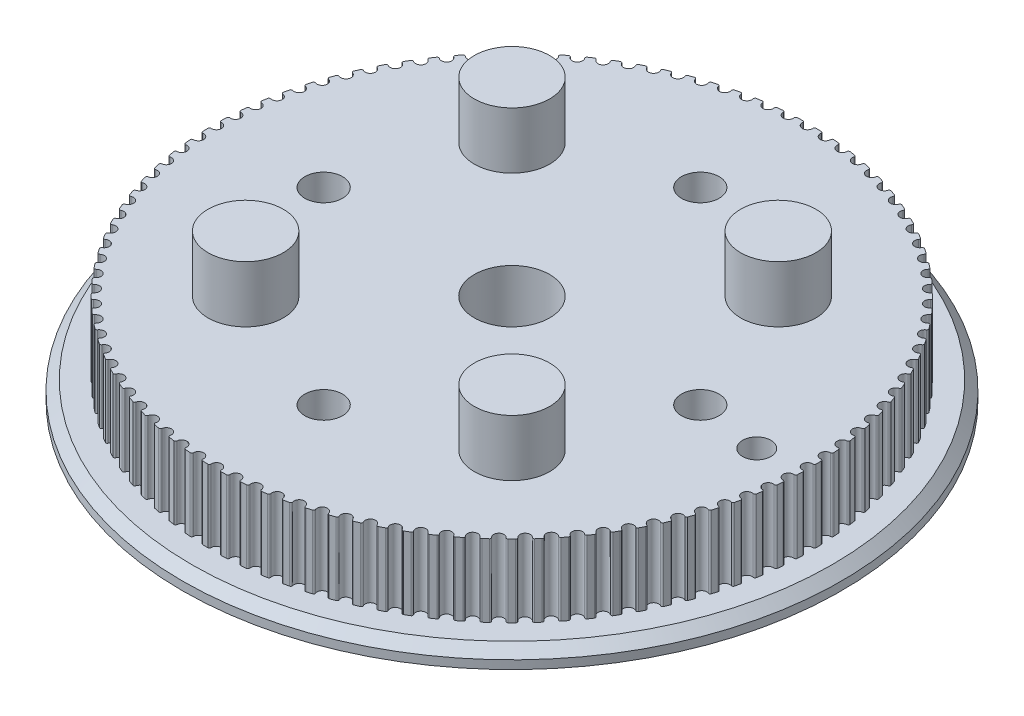
SolidWorks part; units mm, degrees
material "PLA Generic"
ref_plane "Front Plane" through (0, 0, 0) normal (0, 0, 1) x (1, 0, 0)
ref_plane "Top Plane" through (0, 0, 0) normal (0, 1, 0) x (1, 0, 0)
ref_plane "Right Plane" through (0, 0, 0) normal (1, 0, 0) x (0, 0, -1)
sketch "Sketch1" plane through (0, 0, 0) normal (0, 1, 0) x (1, 0, 0)
  circle A0 centre (0, 0) radius 31.6
  circle A1 centre (0, 0) radius 4
  dimension "D1" = 63.2
  dimension "D2" = 8
extrude "Boss-Extrude1" add sketch "Sketch1" along normal blind 7.7
sketch "Sketch2" plane through (0, 0, 0) normal (0, -1, 0) x (1, 0, 0)
  circle A0 centre (0, 0) radius 31.39 construction
  circle A1 centre (0, 31.39) radius 0.55
  circle A2 centre (0, 0) radius 31.39 construction
  circle A4 centre (0, 0) radius 31.39 construction
  circle A6 centre (0, 0) radius 31.39 construction
  circle A8 centre (0, 0) radius 31.39 construction
  circle A10 centre (0, 0) radius 31.39 construction
  circle A12 centre (0, 0) radius 31.39 construction
  circle A14 centre (0, 0) radius 31.39 construction
  circle A16 centre (0, 0) radius 31.39 construction
  circle A18 centre (0, 0) radius 31.39 construction
  circle A20 centre (0, 0) radius 31.39 construction
  circle A22 centre (0, 0) radius 31.39 construction
  circle A24 centre (0, 0) radius 31.39 construction
  circle A26 centre (0, 0) radius 31.39 construction
  circle A28 centre (0, 0) radius 31.39 construction
  circle A30 centre (0, 0) radius 31.39 construction
  circle A32 centre (0, 0) radius 31.39 construction
  circle A34 centre (0, 0) radius 31.39 construction
  circle A36 centre (0, 0) radius 31.39 construction
  circle A38 centre (0, 0) radius 31.39 construction
  circle A40 centre (0, 0) radius 31.39 construction
  circle A42 centre (0, 0) radius 31.39 construction
  circle A44 centre (0, 0) radius 31.39 construction
  circle A46 centre (0, 0) radius 31.39 construction
  circle A48 centre (0, 0) radius 31.39 construction
  circle A50 centre (0, 0) radius 31.39 construction
  circle A52 centre (0, 0) radius 31.39 construction
  circle A54 centre (0, 0) radius 31.39 construction
  circle A56 centre (0, 0) radius 31.39 construction
  circle A58 centre (0, 0) radius 31.39 construction
  circle A60 centre (0, 0) radius 31.39 construction
  circle A62 centre (0, 0) radius 31.39 construction
  circle A64 centre (0, 0) radius 31.39 construction
  circle A66 centre (0, 0) radius 31.39 construction
  circle A68 centre (0, 0) radius 31.39 construction
  circle A70 centre (0, 0) radius 31.39 construction
  circle A72 centre (0, 0) radius 31.39 construction
  circle A74 centre (0, 0) radius 31.39 construction
  circle A76 centre (0, 0) radius 31.39 construction
  circle A78 centre (0, 0) radius 31.39 construction
  circle A80 centre (0, 0) radius 31.39 construction
  circle A82 centre (0, 0) radius 31.39 construction
  circle A84 centre (0, 0) radius 31.39 construction
  circle A86 centre (0, 0) radius 31.39 construction
  circle A88 centre (0, 0) radius 31.39 construction
  circle A90 centre (0, 0) radius 31.39 construction
  circle A92 centre (0, 0) radius 31.39 construction
  circle A94 centre (0, 0) radius 31.39 construction
  circle A96 centre (0, 0) radius 31.39 construction
  circle A98 centre (0, 0) radius 31.39 construction
  circle A100 centre (0, 0) radius 31.39 construction
  circle A102 centre (0, 0) radius 31.39 construction
  circle A104 centre (0, 0) radius 31.39 construction
  circle A106 centre (0, 0) radius 31.39 construction
  circle A108 centre (0, 0) radius 31.39 construction
  circle A110 centre (0, 0) radius 31.39 construction
  circle A112 centre (0, 0) radius 31.39 construction
  circle A114 centre (0, 0) radius 31.39 construction
  circle A116 centre (0, 0) radius 31.39 construction
  circle A118 centre (0, 0) radius 31.39 construction
  circle A120 centre (0, 0) radius 31.39 construction
  circle A122 centre (0, 0) radius 31.39 construction
  circle A124 centre (0, 0) radius 31.39 construction
  circle A126 centre (0, 0) radius 31.39 construction
  circle A128 centre (0, 0) radius 31.39 construction
  circle A130 centre (0, 0) radius 31.39 construction
  circle A132 centre (0, 0) radius 31.39 construction
  circle A134 centre (0, 0) radius 31.39 construction
  circle A136 centre (0, 0) radius 31.39 construction
  circle A138 centre (0, 0) radius 31.39 construction
  circle A140 centre (0, 0) radius 31.39 construction
  circle A142 centre (0, 0) radius 31.39 construction
  circle A144 centre (0, 0) radius 31.39 construction
  circle A146 centre (0, 0) radius 31.39 construction
  circle A148 centre (0, 0) radius 31.39 construction
  circle A150 centre (0, 0) radius 31.39 construction
  circle A152 centre (0, 0) radius 31.39 construction
  circle A154 centre (0, 0) radius 31.39 construction
  circle A156 centre (0, 0) radius 31.39 construction
  circle A158 centre (0, 0) radius 31.39 construction
  circle A160 centre (0, 0) radius 31.39 construction
  circle A162 centre (0, 0) radius 31.39 construction
  circle A164 centre (0, 0) radius 31.39 construction
  circle A166 centre (0, 0) radius 31.39 construction
  circle A168 centre (0, 0) radius 31.39 construction
  circle A170 centre (0, 0) radius 31.39 construction
  circle A172 centre (0, 0) radius 31.39 construction
  circle A174 centre (0, 0) radius 31.39 construction
  circle A176 centre (0, 0) radius 31.39 construction
  circle A178 centre (0, 0) radius 31.39 construction
  circle A180 centre (0, 0) radius 31.39 construction
  circle A182 centre (0, 0) radius 31.39 construction
  circle A184 centre (0, 0) radius 31.39 construction
  circle A186 centre (0, 0) radius 31.39 construction
  circle A188 centre (0, 0) radius 31.39 construction
  circle A190 centre (0, 0) radius 31.39 construction
  circle A192 centre (0, 0) radius 31.39 construction
  circle A194 centre (0, 0) radius 31.39 construction
  circle A196 centre (0, 0) radius 31.39 construction
  circle A198 centre (0, 0) radius 31.39 construction
  point P305 (0, 0)
  dimension "D2" = 1.1
extrude "Cut-Extrude2" cut sketch "Sketch2" against normal blind 7.7
fillet "Fillet2" radius 0.16 2 edges at (0.51, 3.85, 31.5959) (-0.51, 3.85, 31.5959)
pattern_circular "CirPattern1" count 100 over 360 about axis through (0, 0, 0) along (0, 1, 0) of "Cut-Extrude2", "Fillet2"
sketch "Sketch3" plane through (0, 0, 0) normal (0, -1, 0) x (1, 0, 0)
  circle A0 centre (0, 0) radius 4
  circle A1 centre (0, 0) radius 35
  dimension "D1" = 70
extrude "Boss-Extrude2" add sketch "Sketch3" along normal blind 1.9
sketch "Sketch4" plane through (0, -1.9, 0) normal (0, -1, 0) x (1, 0, 0)
  circle A0 centre (0, 20) radius 2
  circle A1 centre (20, 0) radius 2
  circle A2 centre (0, -20) radius 2
  circle A3 centre (-20, 0) radius 2
  point P12 (0, 0)
  dimension "D1" = 20
  dimension "D2" = 4
  dimension "D3" = 4
extrude "Cut-Extrude3" cut sketch "Sketch4" against normal through all
sketch "Sketch5" plane through (0, -1.9, 0) normal (0, -1, 0) x (1, 0, 0)
  circle A0 centre (0, 20) radius 3.7
  circle A1 centre (20, 0) radius 3.7
  circle A2 centre (0, -20) radius 3.7
  circle A3 centre (-20, 0) radius 3.7
  point P12 (0, 0)
  dimension "D1" = 7.4
  dimension "D2" = 4
extrude "Cut-Extrude4" cut sketch "Sketch5" against normal blind 4
chamfer "Chamfer1" distance 1 angle 45 1 edges at (0, 0, -35)
sketch "Sketch6" plane through (0, 7.7, 0) normal (0, 1, 0) x (1, 0, 0)
  line L0 (0, 0) -> (23.4245, 0) construction
  line L1 (0, 0) -> (14.1421, 14.1421) construction
  circle A0 centre (14.1421, 14.1421) radius 4
  circle A1 centre (14.1421, -14.1421) radius 4
  circle A2 centre (-14.1421, -14.1421) radius 4
  circle A3 centre (-14.1421, 14.1421) radius 4
  point P14 (0, 0)
  dimension "D3" = 8
  dimension "D1" = 45
  dimension "D2" = 20
  dimension "D4" = 4
extrude "Boss-Extrude3" add sketch "Sketch6" along normal blind 6
sketch "Sketch7" plane through (0, -1.9, 0) normal (0, -1, 0) x (1, 0, 0)
  line L0 (0, 0) -> (0, 1) construction
  line L1 (0, 1) -> (27, 1) construction
  circle A0 centre (27, 1) radius 1.5
  dimension "D3" = 3
  dimension "D1" = 27
  dimension "D2" = 1
extrude "Cut-Extrude5" cut sketch "Sketch7" against normal through all
